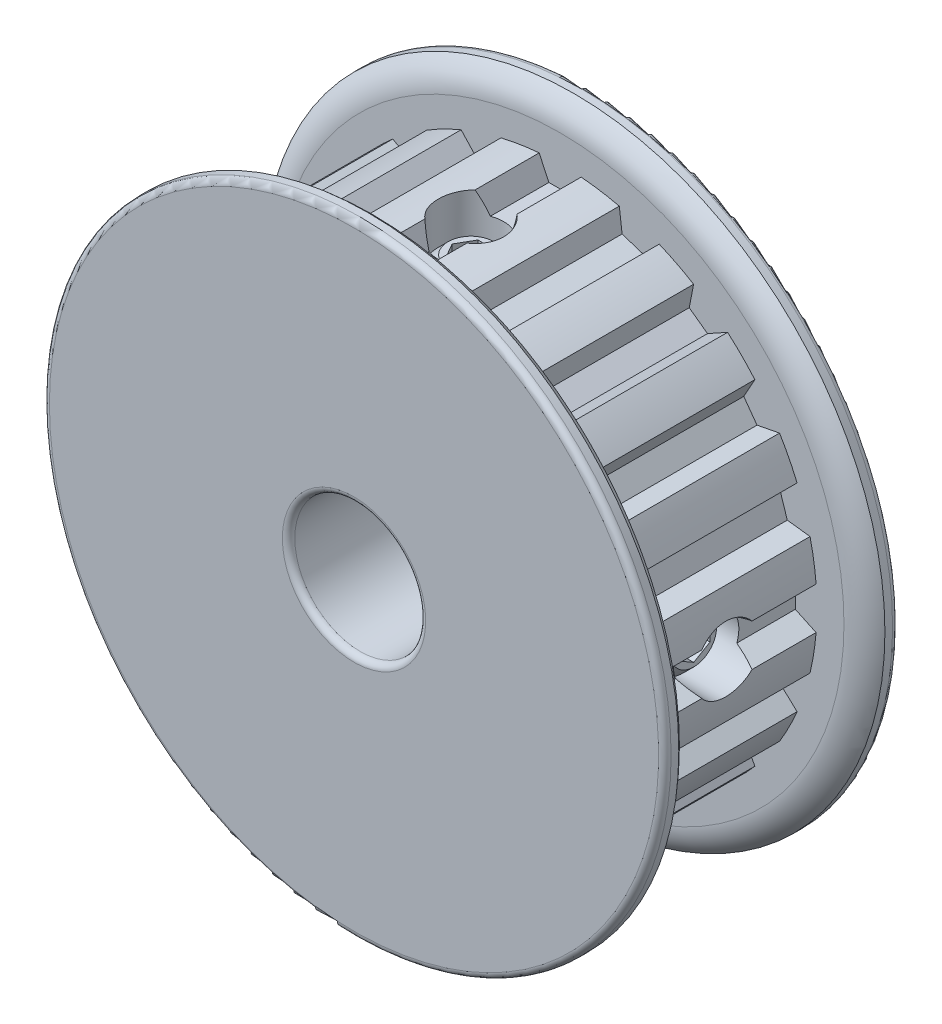
SolidWorks part; units mm, degrees
note: '?' marks a value the reader was unsure of.
ref_plane "Front Plane" through (0, 0, 0) normal (0, 0, 1) x (1, 0, 0)
ref_plane "Top Plane" through (0, 0, 0) normal (0, 1, 0) x (1, 0, 0)
ref_plane "Right Plane" through (0, 0, 0) normal (1, 0, 0) x (0, 0, -1)
sketch "Sketch1" plane through (0, 0, 0) normal (0, 0, 1) x (1, 0, 0)
  line L0 (-1.2827, 15.642) -> (-0.6905, 14.372)
  line L1 (-0.6905, 14.372) -> (0.6905, 14.372)
  line L2 (0.6905, 14.372) -> (1.2827, 15.642)
  line L3 (-1.2827, 15.642) -> (1.2827, 15.642)
  line L4 (0, 0) -> (0, 14.372) construction
  line L5 (0, 14.372) -> (0, 16.658) construction
  circle A0 centre (0, 0) radius 16.15 construction
  circle A1 centre (0, 0) radius 19 construction
  circle A2 centre (0, 0) radius 15.6945 construction
  point P6 (0, 15.642)
  point P11 (0, 16.15)
  point P13 (0, 19)
  point P14 (0, 15.6945)
  dimension "D1" = 1.016
  dimension "PD" = 32.3
  dimension "D2" = 0.508
  dimension "OD" = 38
  dimension "b" = 50
  dimension "bt" = 2.5654
  dimension "ht" = 1.27
  dimension "hs" = 2.286
sketch "Sketch2" plane through (0, 0, 0) normal (1, 0, 0) x (0, 0, -1)
  line L0 (-7.15, 4) -> (7.15, 4)
  line L3 (-7.15, 4) -> (-7.15, 19)
  line L4 (-7.15, 19) -> (-5.45, 19) construction
  line L5 (-5.45, 19) -> (-5.45, 15.6945) construction
  line L6 (-5.45, 15.6945) -> (5.45, 15.6945)
  line L7 (5.45, 15.6945) -> (5.45, 19) construction
  line L8 (5.45, 19) -> (7.15, 19) construction
  line L9 (7.15, 19) -> (7.15, 4)
  line L10 (-7.15, 0) -> (7.15, 0) construction
  line L13 (-7.15, 19) -> (-6.3, 19)
  line L14 (-5.45, 17.3473) -> (-5.45, 15.6945)
  line L15 (5.45, 15.6945) -> (5.45, 17.3473)
  line L16 (6.3, 19) -> (7.15, 19)
  arc A0 (-5.45, 17.3473) -> (-6.3, 19) centre (-7.4818, 17.3473) ccw
  arc A1 (5.45, 17.3473) -> (6.3, 19) centre (7.4818, 17.3473) cw
  point P12 (-5.45, 17.3473)
  point P14 (-6.3, 19)
  point P20 (5.45, 17.3473)
  point P21 (6.3, 19)
  point P25 (5.45, 0)
  point P26 (-5.45, 0)
  dimension "OA" = 14.3
  dimension "Bore" = 8
  dimension "Outside Width" = 14.3
  dimension "Inside Width" = 10.9
revolve "Revolve1" add sketch "Sketch2" angle 360 mid plane about L10
sketch "Sketch3" plane through (0, 0, 0) normal (0, 0, 1) x (1, 0, 0)
  line L0 (-0.6905, 14.372) -> (0.6905, 14.372) construction
  line L1 (0.6905, 14.372) -> (1.2827, 15.642) construction
  line L2 (-1.2827, 15.642) -> (-0.6905, 14.372) construction
  line L3 (-0.6905, 14.372) -> (0.6905, 14.372)
  line L4 (0.6905, 14.372) -> (1.2827, 15.642)
  line L5 (-1.2827, 15.642) -> (-0.6905, 14.372)
  circle A0 centre (0, 0) radius 15.6945 construction
  arc A1 (1.2827, 15.642) -> (-1.2827, 15.642) centre (0, 0) ccw
extrude "Cut-Extrude1" cut sketch "Sketch3" against normal up to vertex (5.45 mm away) from vertex at 5.45 starting at point (0, 15.6945, 5.45)
pattern_circular "CirPattern1" count 20 over 360 about axis through (0, 0, 0) along (0, 0, 1) of "Cut-Extrude1"
fillet "Fillet1" radius 0.381 4 edges at (4, 0, -7.15) (19, 0, -7.15) (19, 0, 7.15) (4, 0, 7.15)
sketch "Sketch5" plane through (0, 0, 0) normal (0, 1, 0) x (1, 0, 0)
  line L1 (1.2827, 0) -> (-1.2827, 0) construction
  line L2 (1.2827, 5.45) -> (1.2827, -5.45) construction
  line L3 (-1.2827, 5.45) -> (-1.2827, -5.45) construction
  circle A0 centre (0, 0) radius 2
extrude "Cut-Extrude2" cut sketch "Sketch5" along normal through all
sketch "Sketch6" plane through (0, 0, 0) normal (1, 0, 0) x (0, 0, -1)
  line L0 (0, 13.61) -> (0, 4.762)
  line L1 (6.769, 4) -> (-6.769, 4) construction
  line L3 (2, 14.372) -> (-2, 14.372) construction
  line L4 (-1.877, 14.372) -> (-2, 14.372) construction
  line L5 (2, 14.372) -> (1.877, 14.372) construction
  line L6 (0, 13.61) -> (-1.4, 13.61)
  line L7 (-1.4, 13.61) -> (-2, 13.01)
  line L8 (-2, 13.01) -> (-2, 5.362)
  line L9 (-2, 5.362) -> (-1.4, 4.762)
  line L10 (-1.4, 4.762) -> (0, 4.762)
  point P12 (0, 4)
  point P19 (0, 14.372)
  dimension "D1" = 0.762
  dimension "D2" = 0.762
  dimension "D3" = 135
  dimension "D4" = 0.6
revolve "Revolve2" add sketch "Sketch6" angle 360 about L0
sketch "Sketch7" plane through (0, 13.61, 0) normal (0, 1, 0) x (1, 0, 0)
  line L1 (1.1547, 0) -> (0.5774, 1)
  line L2 (0.5774, 1) -> (-0.5774, 1)
  line L3 (-0.5774, 1) -> (-1.1547, 0)
  line L4 (-1.1547, 0) -> (-0.5774, -1)
  line L5 (-0.5774, -1) -> (0.5774, -1)
  line L6 (0.5774, -1) -> (1.1547, 0)
  circle A0 centre (0, 0) radius 1 construction
  dimension "D1" = 2
extrude "Cut-Extrude3" cut sketch "Sketch7" against normal blind 1
pattern_circular "CirPattern2" count 2 over 270 about axis through (0, 0, 0) along (0, 0, 1) of "Cut-Extrude2", "Revolve2", "Cut-Extrude3"
ref_axis "Center Axis 1" through (0, 0, -6.769) along (0, 0, 1)?
ref_plane "Contact Plane 1" through (0, 0, 7.15) normal (0, 0, 1) x (1, 0, 0)
ref_plane "Contact Plane 2" through (0, 0, -7.15) normal (0, 0, -1) x (-1, 0, 0)
equation "\"D4@Sketch6\" = \"Set Screw Dia@Sketch5\" * .15"
equation "\"D1@Sketch7\" = \"Set Screw Dia@Sketch5\" / 2"
equation "\"D1@Cut-Extrude3\" = \"Set Screw Dia@Sketch5\" / 4"
